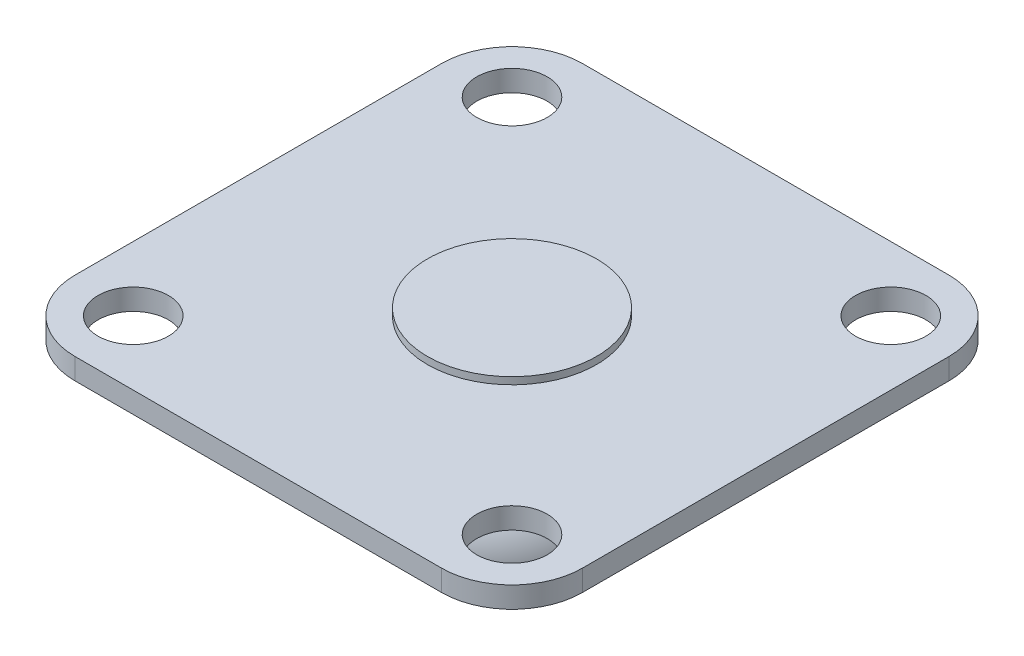
SolidWorks part; units mm, degrees
ref_plane "Front Plane" through (0, 0, 0) normal (0, 0, 1) x (1, 0, 0)
ref_plane "Top Plane" through (0, 0, 0) normal (0, 1, 0) x (1, 0, 0)
ref_plane "Right Plane" through (0, 0, 0) normal (1, 0, 0) x (0, 0, -1)
sketch "Sketch1" plane through (0, 0, 0) normal (0, 1, 0) x (1, 0, 0)
  line L0 (-13.435, -13.435) -> (13.435, 13.435)
  line L1 (-13, -18) -> (13, -18)
  line L2 (-18, -13) -> (-18, 13)
  line L3 (-13, 18) -> (13, 18)
  line L4 (18, -13) -> (18, 13)
  line L5 (-18, -18) -> (18, 18) construction
  line L6 (-18, 18) -> (18, -18) construction
  arc A0 (13, -18) -> (18, -13) centre (13, -13) ccw
  arc A1 (-13, -18) -> (-18, -13) centre (-13, -13) cw
  arc A2 (-18, 13) -> (-13, 18) centre (-13, 13) cw
  arc A3 (13, 18) -> (18, 13) centre (13, 13) cw
  circle A4 centre (13.435, 13.435) radius 2.5
  circle A5 centre (-13.435, -13.435) radius 2.5
  circle A6 centre (-13.435, 13.435) radius 2.5
  circle A7 centre (13.435, -13.435) radius 2.5
  point P0 (0, 0)
  point P21 (0, 0)
  dimension "D3" = 5
  dimension "D5" = 5
  dimension "D6" = 5
  dimension "D7" = 5
  dimension "D8" = 5
  dimension "D1" = 36
  dimension "D2" = 36
  dimension "D4" = 38
extrude "Boss-Extrude1" add sketch "Sketch1" along normal blind 1.5 contours A3 L3 A2 L2 A1 L1 A0 L4 A7 A6 A5 A4 region at (-16.1755, 0, 16.1755)
sketch "Sketch2" plane through (0, 0, 0) normal (0, -1, 0) x (1, 0, 0)
  circle A0 centre (0, 0) radius 6
  dimension "D1" = 12
extrude "Boss-Extrude2" add sketch "Sketch2" along normal blind 4 and the other way blind 2
ref_plane "Plane1" through (0, -3, 0) normal (0, -1, 0) x (-1, 0, 0)
sketch "Sketch3" plane through (0, -3, 0) normal (0, -1, 0) x (-1, 0, 0)
  circle A0 centre (0, 0) radius 6
  circle A1 centre (0, 0) radius 9
  dimension "D1" = 18
extrude "Boss-Extrude3" add sketch "Sketch3" along normal blind 5
fillet "Fillet1" radius 5 1 edges at (0, -3, -9)
